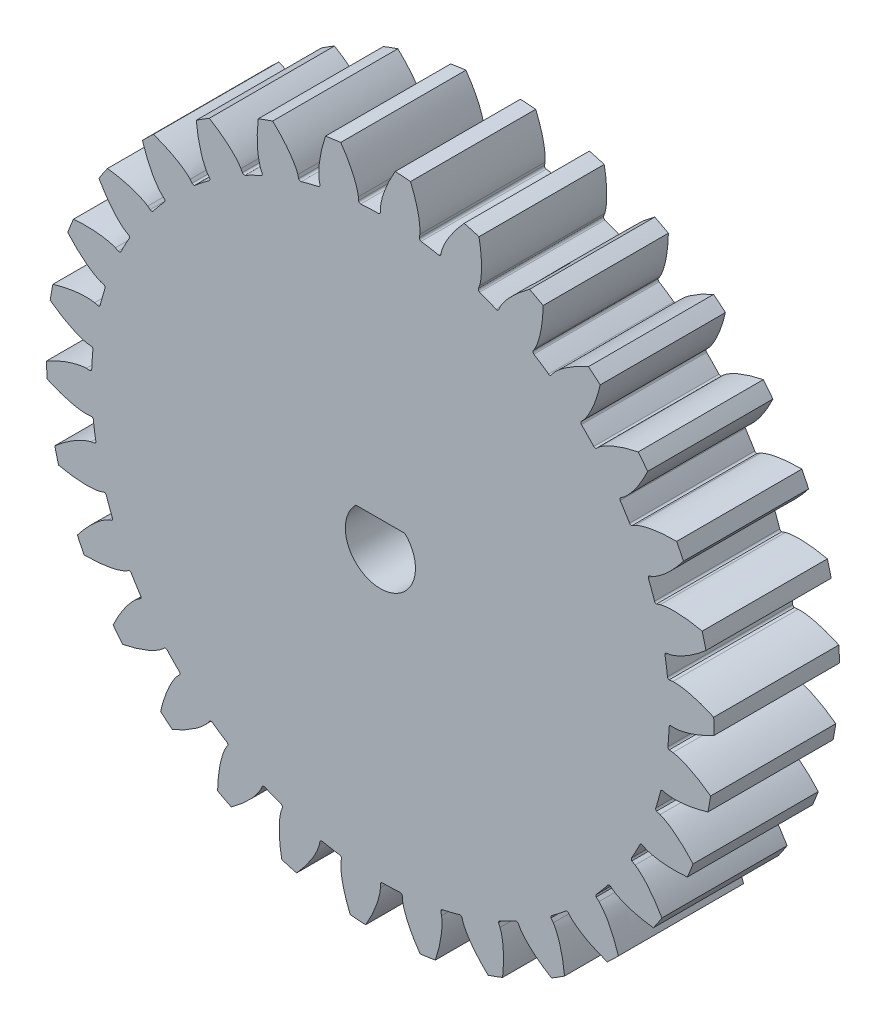
SolidWorks part; units mm, degrees
ref_plane "Alzado" through (0, 0, 0) normal (0, 0, 1) x (1, 0, 0)
ref_plane "Planta" through (0, 0, 0) normal (0, 1, 0) x (1, 0, 0)
ref_plane "Vista lateral" through (0, 0, 0) normal (1, 0, 0) x (0, 0, -1)
sketch "Croquis1" plane through (0, 0, 0) normal (0, 0, 1) x (1, 0, 0)
  line L0 (0, 0) -> (131.0885, 0) construction
  line L1 (0, 0) -> (0, 30) construction
  line L2 (0, 0) -> (12.4587, 12.4587) construction
  line L3 (12.4587, 12.4587) -> (2.6737, 22.2437) construction
  line L4 (0, 0) -> (11.3254, 13.4971) construction
  line L5 (11.3254, 13.4971) -> (1.9027, 21.4038) construction
  line L6 (0, 0) -> (10.106, 14.4328) construction
  line L7 (10.106, 14.4328) -> (1.2895, 20.6062) construction
  line L8 (0, 0) -> (8.8096, 15.2587) construction
  line L9 (8.8096, 15.2587) -> (0.8202, 19.8714) construction
  line L10 (0, 0) -> (7.4462, 15.9685) construction
  line L11 (7.4462, 15.9685) -> (0.4787, 19.2175) construction
  line L12 (0, 0) -> (6.0261, 16.5567) construction
  line L13 (6.0261, 16.5567) -> (0.2468, 18.6602) construction
  line L14 (0, 0) -> (4.5602, 17.0189) construction
  line L15 (4.5602, 17.0189) -> (0.1047, 18.2127) construction
  line L16 (0, 0) -> (3.0595, 17.3516) construction
  line L17 (3.0595, 17.3516) -> (0.0311, 17.8856) construction
  line L18 (0, 0) -> (1.5356, 17.5522) construction
  line L19 (1.5356, 17.5522) -> (0.0039, 17.6862) construction
  circle A0 centre (0, 0) radius 17.6192 construction
  circle A1 centre (0, 0) radius 17.3038 construction
  circle A2 centre (0, 0) radius 20 construction
  circle A3 centre (0, 0) radius 18.75 construction
  spline S0 degree 3 poles (0, 17.6192) (0.003, 17.7087) (0.0309, 17.9084) (0.1107, 18.2574) (0.255, 18.7048) (0.4889, 19.2621) (0.8326, 19.916) (1.5096, 20.9709) (2.1682, 21.7377) (2.6737, 22.2437) knots 0 0 0 0 0.049384 0.111113 0.197533 0.308643 0.444446 0.604939 1 1 1 1
  point P3 (87.284, 1.25)
  point P4 (102.0506, 30)
  point P5 (119.8936, 20)
  point P29 (0, 17.6192)
  dimension "Diámetro de paso (D)" = 37.5
  dimension "Diámetro de raiz" = 34.6075
  dimension "D1" = 40
  dimension "D2" = 35.2385
  dimension "Módulo (m)" = 1.25
  dimension "Número de dientes (N)" = 30
  dimension "Ángulo de presión (AP)" = 20
  dimension "D3" = 45
  dimension "D4" = 13.8381
  dimension "D5" = 40
  dimension "D6" = 12.3005
  dimension "D7" = 35
  dimension "D8" = 10.763
  dimension "D9" = 9.2254
  dimension "D10" = 30
  dimension "D11" = 25
  dimension "D12" = 7.6878
  dimension "D13" = 20
  dimension "D14" = 6.1503
  dimension "D15" = 15
  dimension "D16" = 4.6127
  dimension "D17" = 10
  dimension "D18" = 3.0751
  dimension "D19" = 5
  dimension "D20" = 1.5376
sketch "Croquis2" plane through (0, 0, 0) normal (0, 0, 1) x (1, 0, 0)
  line L0 (56.3227, 9.5882) -> (76.5884, 9.5882) construction
  line L1 (0, 17.3911) -> (0, 17.6192)
  line L2 (0, 0) -> (0.3802, 25.5087) construction
  line L3 (0, 0) -> (3.1082, 25.8589) construction
  line L4 (0, 0) -> (32.6464, 0) construction
  line L5 (0, 0) -> (131.0885, 0) construction
  line L6 (0, 0) -> (1.6991, 25.221) construction
  line L7 (2.3325, 17.2754) -> (2.3632, 17.46)
  line L8 (57.5292, -20.4598) -> (78.7754, -20.4598) construction
  line L9 (0, 0) -> (0, -1.4) construction
  circle A0 centre (0, 0) radius 17.3038 construction
  circle A1 centre (0, 0) radius 20 construction
  arc A2 (-0.1185, 17.3033) -> (2.4382, 17.1311) centre (0, 0) ccw
  arc A3 (1.8037, 19.9185) -> (0.8841, 19.9804) centre (0, 0) ccw
  circle A4 centre (0, 0) radius 18.75 construction
  circle A5 centre (0, 0) radius 2.1
  arc A6 (2.3325, 17.2754) -> (2.4382, 17.1311) centre (2.4558, 17.2549) ccw
  arc A7 (0, 17.3911) -> (-0.1185, 17.3033) centre (-0.1193, 17.4283) cw
  spline S0 degree 3 poles (3999.154, -11.1559) (22.4729, -2.4419) (-1.6764, 10.4482) (0.1107, 18.2574) (0.255, 18.7048) (0.4889, 19.2621) (0.8326, 19.916) (24.6889, 57.0873) (266.2192, -59.859) (-3996.4932, 54.198) knots -4.222676 -4.222676 -4.222676 -4.222676 0.049384 0.111113 0.197533 0.308643 0.444446 0.604939 24.668661 24.668661 24.668661 24.668661 only from (0, 17.6192) to (2.6737, 22.2437) construction
  spline S1 degree 3 poles (0, 17.6192) (0.003, 17.7087) (0.0309, 17.9084) (0.1107, 18.2574) (0.255, 18.7048) (0.4889, 19.2621) (0.7168, 19.6957) (0.8626, 19.9442) (0.8841, 19.9804) knots 0 0 0 0 0.049384 0.111113 0.197533 0.308643 0.444446 0.467706 0.467706 0.467706 0.467706
  spline S2 degree 3 poles (2.3632, 17.46) (2.3722, 17.5491) (2.3714, 17.7508) (2.339, 18.1073) (2.2561, 18.57) (2.0991, 19.1536) (1.9314, 19.6139) (1.8202, 19.8797) (1.8037, 19.9185) knots 0 0 0 0 0.049384 0.111113 0.197533 0.308643 0.444446 0.467706 0.467706 0.467706 0.467706
  point P8 (0.2795, 18.7479)
  point P13 (28.0519, 1.9635)
  point P22 (68.2533, 14.5882)
  point P25 (68.2533, 9.5402)
  dimension "Diámetro del cubo" = 4.2
  dimension "Redondeo" = 0.125
  dimension "Espesor del diente (T)" = 1.9635
  dimension "D1" = 6
  dimension "D2" = 3
  dimension "Espesor del engrane" = 5
  dimension "dientes" = 30
extrude "Saliente-Extruir1" add sketch "Croquis2" along normal blind 7.5
pattern_circular "MatrizC6" count 30 over 360 about axis through (0, 0, 7.5) along (0, 0, -1) of "Saliente-Extruir1"
sketch "Croquis6" plane through (0, 0, 7.5) normal (0, 0, 1) x (1, 0, 0)
  line L0 (0, 0) -> (0, 1.5) construction
  line L1 (0, 1.5) -> (1.4697, 1.5)
  line L2 (0, 1.5) -> (-1.4697, 1.5)
  circle A0 centre (0, 0) radius 2.1 construction
  arc A1 (1.4697, 1.5) -> (-1.4697, 1.5) centre (0, 0) ccw
  dimension "D1" = 1.5
extrude "Saliente-Extruir2" add sketch "Croquis6" against normal blind 7.5
equation "\"Diámetro de paso (D)@Croquis1\"=\"Módulo (m)@Croquis1\"*\"Número de dientes (N)@Croquis1\""
equation "\"Diámetro de raiz@Croquis1\"=(\"Diámetro de paso (D)@Croquis1\")-((2.314)*(\"Módulo (m)@Croquis1\"))"
equation "\"D1@Croquis1\"=(\"Diámetro de paso (D)@Croquis1\")+((2)*(\"Módulo (m)@Croquis1\"))"
equation "\"D2@Croquis1\"=(\"Diámetro de paso (D)@Croquis1\")*(cos( \"Ángulo de presión (AP)@Croquis1\"))"
equation "\"D4@Croquis1\"=(\"D2@Croquis1\"/(2))*((\"D3@Croquis1\")*(PI)/(180))"
equation "\"D6@Croquis1\"=(\"D2@Croquis1\"/(2))*((\"D5@Croquis1\")*(PI)/(180))"
equation "\"D8@Croquis1\"=(\"D2@Croquis1\"/(2))*((\"D7@Croquis1\")*(PI)/(180))"
equation "\"D9@Croquis1\"=(\"D2@Croquis1\"/(2))*((\"D10@Croquis1\")*(PI)/(180))"
equation "\"D12@Croquis1\"=(\"D2@Croquis1\"/(2))*((\"D11@Croquis1\")*(PI)/(180))"
equation "\"D14@Croquis1\"=(\"D2@Croquis1\"/(2))*((\"D13@Croquis1\")*(PI)/(180))"
equation "\"D16@Croquis1\"=(\"D2@Croquis1\"/(2))*((\"D15@Croquis1\")*(PI)/(180))"
equation "\"D18@Croquis1\"=(\"D2@Croquis1\"/(2))*((\"D17@Croquis1\")*(PI)/(180))"
equation "\"D20@Croquis1\"=(\"D2@Croquis1\"/(2))*((\"D19@Croquis1\")*(PI)/(180))"
equation "\"Espesor del diente (T)@Croquis2\"=(1.5708)*(\"Módulo (m)@Croquis1\")"
equation "\"D1@Croquis2\"=(\"Espesor del diente (T)@Croquis2\"/(\"Diámetro de paso (D)@Croquis1\"/2))*(180/PI)"
equation "\"D2@Croquis2\"=\"D1@Croquis2\"/2"
equation "\"dientes@Croquis2\"=\"Número de dientes (N)@Croquis1\""
equation "\"Redondeo@Croquis2\"=\"Módulo (m)@Croquis1\"*(0.1)"
equation "\"D1@MatrizC6\"=\"Número de dientes (N)@Croquis1\""
